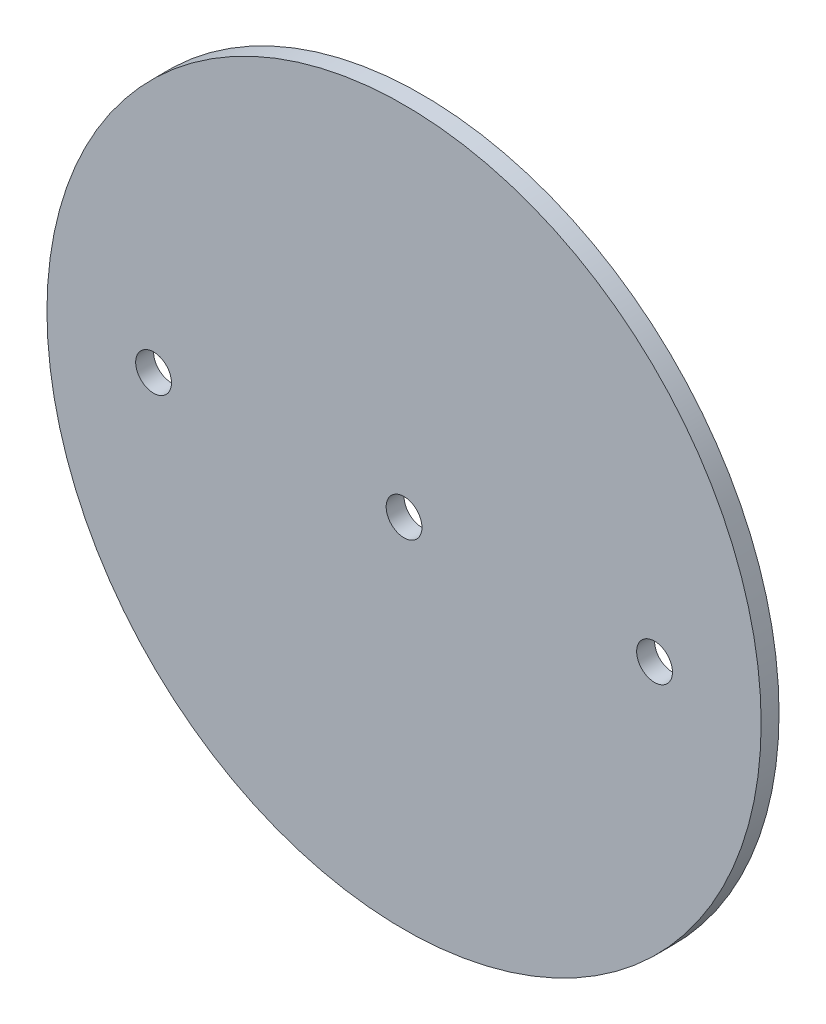
SolidWorks part; units mm, degrees
ref_plane "Front Plane" through (0, 0, 0) normal (0, 0, 1) x (1, 0, 0)
ref_plane "Top Plane" through (0, 0, 0) normal (0, 1, 0) x (1, 0, 0)
ref_plane "Right Plane" through (0, 0, 0) normal (1, 0, 0) x (0, 0, -1)
sketch "Sketch1" plane through (0, 0, 0) normal (0, 0, 1) x (1, 0, 0)
  circle A0 centre (0, 0) radius 63.373
  dimension "D1" = 126.746
extrude "Boss-Extrude1" add sketch "Sketch1" along normal mid plane 3.175
sketch "Sketch2" plane through (0, 0, 1.5875) normal (0, 0, 1) x (1, 0, 0)
  line L0 (-1000, 0) -> (49000, 0) construction
  point P1 (0, 0)
  point P4 (44.45, 0)
  point P5 (-44.45, 0)
  dimension "D1" = 44.45
  dimension "D2" = 88.9
hole_wizard "1/4 (0.25) Diameter Hole1" positions "Sketch2" profile "Sketch3" hole size "1/4" standard "ANSI Inch" end condition through all
sketch "Sketch3" plane through (-44.45, 0, 1.5875) normal (1, 0, 0) x (0, -1, 0)
  line L0 (0, 0) -> (0, 3.175)
  line L1 (0, 3.175) -> (3.175, 3.175)
  line L2 (3.175, 3.175) -> (3.175, 0)
  line L5 (3.175, 0) -> (0, 0)
  line L11 (0, -6.35) -> (0, 107.95) construction
  dimension "Thru Hole Dia." = 6.35
  dimension "Thru Hole Depth" = 3.175
equation "\"AIRFRAME_OD\"= 5.15in"
equation "\"AIRFRAME_ID\"= 4.99in"
equation "\"FLAT_T\"= 0.125in"
equation "\"NOSE_EXP_L\"= 27in"
equation "\"NOSE_SHOULDER_L\"= 5in"
equation "\"MAIN_L\"= 30in"
equation "\"RECO_COUP_L\"= 10in"
equation "\"RECO_SWITCH_L\"= 2in"
equation "\"DROGUE_L\"= 20in"
equation "\"ATS_FORE_COUP_L\"= 5.5in"
equation "\"ATS_AFT_COUP_L\"= 4.5in"
equation "\"LOWER_L\"= 30in"
equation "\"FIN_N\"= 4"
equation "\"CR_AFT_X\"= 0.5in"
equation "\"CR_FORE_X\"= 9.25in"
equation "\"FIN_ROOT\"= 8in"
equation "\"FIN_X\"= 0.75in"
equation "\"MOTOR_OD\"= 3.091in"
equation "\"MOTOR_ID\"= 3.00in"
equation "\"COUPLER_OD\"= 4.998in"
equation "\"COUPLER_ID\"= 4.85in"
equation "\"D1@Sketch1\"=\"AIRFRAME_ID\""
equation "\"D1@Boss-Extrude1\"=\"FLAT_T\""
equation "\"RECO_ROD_X\"= 3.5in"
equation "\"ATS_ROD_X\"= 3.75in"
equation "\"D1@Sketch2\"=\"RECO_ROD_X\"*0.5"
equation "\"D2@Sketch2\"=\"RECO_ROD_X\""
equation "\"MOTOR_L\"= 14in"
equation "\"MOTOR_LOWER_X\"= 2in"
